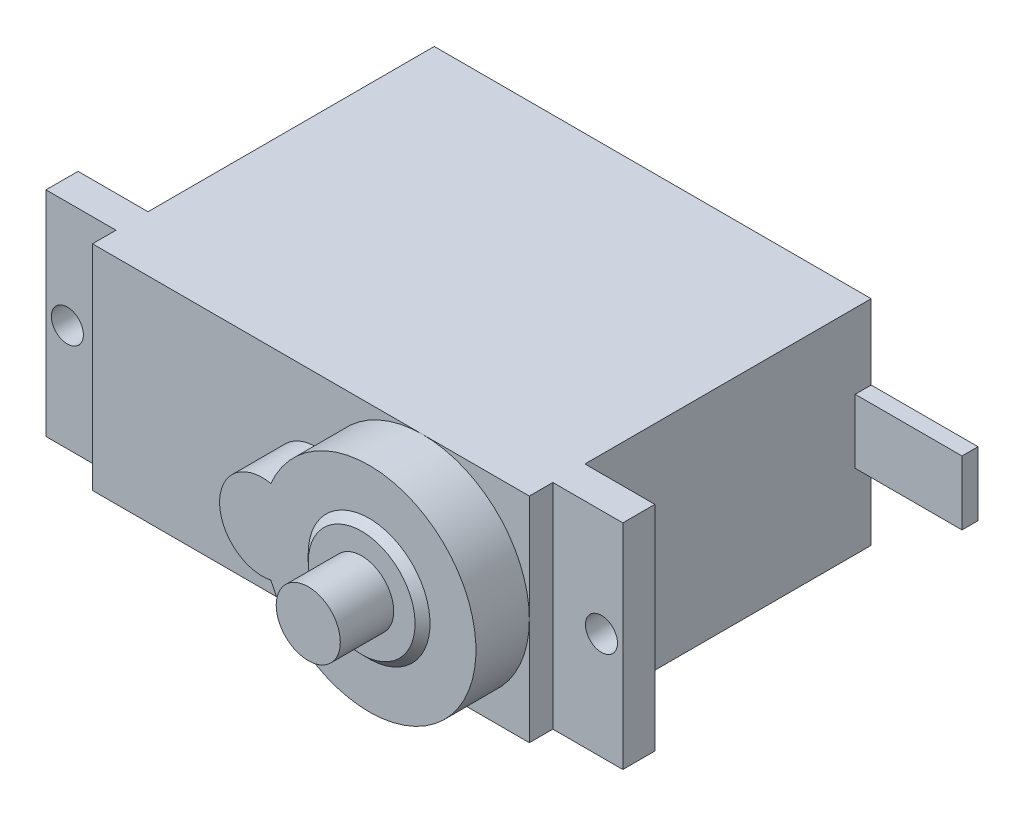
SolidWorks part; units mm, degrees
ref_plane "Top Plane" through (0, 0, 0) normal (0, 0, 1) x (1, 0, 0)
ref_plane "Right Plane" through (0, 0, 0) normal (0, 1, 0) x (1, 0, 0)
ref_plane "Front Plane" through (0, 0, 0) normal (1, 0, 0) x (0, 0, -1)
sketch "Sketch3" plane through (0, 0, 0) normal (0, 0, 1) x (1, 0, 0)
  circle A0 centre (0, 0) radius 3
  dimension "D1" = 6
extrude "Boss-Extrude1" add sketch "Sketch3" along normal mid plane 5
sketch "Sketch4" plane through (0, 0, -2.5) normal (0, 0, -1) x (-1, 0, 0)
  circle A0 centre (0, 0) radius 6
  dimension "D1" = 12
extrude "Boss-Extrude2" add sketch "Sketch4" along normal blind 0.7
sketch "Sketch5" plane through (0, 0, -3.2) normal (0, 0, -1) x (-1, 0, 0)
  arc A0 (9.2, 3.9192) -> (9.2, -3.9192) centre (0, 0) ccw
  arc A1 (9.2, -3.9192) -> (9.2, 3.9192) centre (10, 0) ccw
  point P5 (10, 0)
  dimension "D1" = 20
  dimension "D2" = 8
extrude "Boss-Extrude3" add sketch "Sketch5" along normal blind 5
sketch "Sketch6" plane through (0, 0, -8.2) normal (0, 0, -1) x (-1, 0, 0)
  line L0 (-10, 0) -> (0, 0) construction
  line L1 (-10, 10) -> (30.9, 10)
  line L2 (-10, 10) -> (-10, -10)
  line L3 (-10, -10) -> (30.9, -10)
  line L4 (30.9, 10) -> (30.9, -10)
  dimension "D1" = 10
  dimension "D2" = 20
  dimension "D3" = 40.9
extrude "Boss-Extrude4" add sketch "Sketch6" along normal blind 32
sketch "Sketch7" plane through (10, 0, 0) normal (1, 0, 0) x (0, 0, -1)
  line L0 (40.2, 10) -> (8.2, 10) construction
  line L1 (10.4, 10) -> (13.4, 10)
  line L2 (10.4, 10) -> (10.4, -10)
  line L3 (10.4, -10) -> (13.4, -10)
  line L4 (13.4, 10) -> (13.4, -10)
  line L5 (40.2, -10) -> (8.2, -10) construction
  line L6 (40.2, 10) -> (40.2, -10) construction
  dimension "D1" = 3
  dimension "D2" = 26.8
extrude "Boss-Extrude5" add sketch "Sketch7" along normal blind 20
ref_plane "Plane1" through (-10.45, 0, 0) normal (1, 0, 0) x (0, 0, -1)
mirror "Mirror1" about plane through (-10.45, 0, 0) normal (1, 0, 0) of "Boss-Extrude5"
sketch "Sketch8" plane through (0, 0, 0) normal (0, 0, 1) x (1, 0, 0)
  line L0 (-37.45, -15) -> (16.55, 15) construction
  line L1 (-37.45, -15) -> (16.55, -15)
  line L2 (-37.45, -15) -> (-37.45, 15)
  line L3 (-37.45, 15) -> (16.55, 15)
  line L4 (16.55, -15) -> (16.55, 15)
  line L5 (-10.45, -11) -> (-10.45, 11) construction
  line L6 (-10.45, 0) -> (0, 0) construction
  point P4 (-10.45, 0)
  dimension "D1" = 30
  dimension "D2" = 54
extrude "Cut-Extrude1" cut sketch "Sketch8" against normal through all flip side to cut
sketch "Sketch10" plane through (0, 0, -10.4) normal (0, 0, 1) x (1, 0, 0)
  line L0 (-10.45, -11) -> (-10.45, 11) construction
  line L1 (-10.45, -10.076) -> (-10.45, 10.0003) construction
  line L2 (-37.45, 10) -> (-37.45, -10) construction
  line L3 (-35.45, 0) -> (14.55, 0) construction
  circle A0 centre (-35.45, 0) radius 1.5
  circle A1 centre (14.55, 0) radius 1.5
  dimension "D1" = 3
  dimension "D2" = 2
extrude "Cut-Extrude2" cut sketch "Sketch10" against normal up to next
sketch "Sketch11" plane through (10, 0, 0) normal (1, 0, 0) x (0, 0, -1)
  line L0 (40.2, 10) -> (40.2, -10) construction
  line L1 (38.7, 3) -> (40.2, 3)
  line L2 (38.7, 3) -> (38.7, -3)
  line L3 (38.7, -3) -> (40.2, -3)
  line L4 (40.2, 3) -> (40.2, -3)
  line L5 (38.7, 3) -> (40.2, -3) construction
  line L6 (39.45, 0) -> (0, 0) construction
  dimension "D1" = 1.5
  dimension "D2" = 6
extrude "Boss-Extrude6" add sketch "Sketch11" along normal blind 10
chamfer "Chamfer1" distance 1 angle 45 1 edges at (-6, 0, -2.5)
